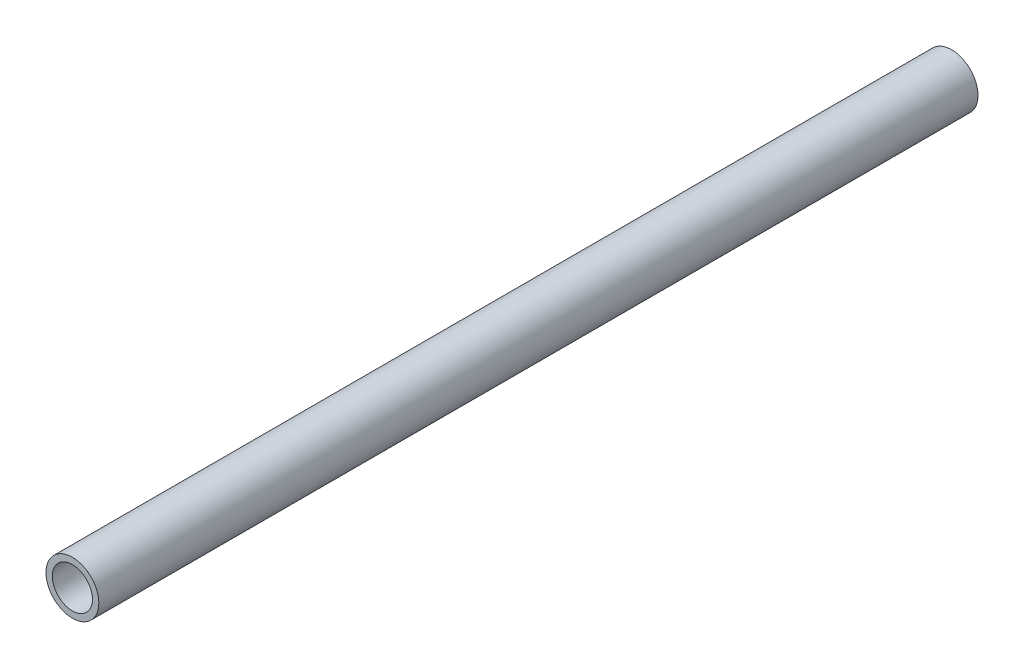
SolidWorks part; units mm, degrees
material "AISI 1020"
ref_plane "Plan de face" through (0, 0, 0) normal (0, 0, 1) x (1, 0, 0)
ref_plane "Plan de dessus" through (0, 0, 0) normal (0, 1, 0) x (1, 0, 0)
ref_plane "Plan de droite" through (0, 0, 0) normal (1, 0, 0) x (0, 0, -1)
sketch "Esquisse1" plane through (0, 0, 0) normal (0, 0, 1) x (1, 0, 0)
  circle A0 centre (0, 0) radius 4.57
  circle A1 centre (0, 0) radius 3.47
  dimension "D1" = 9.14
  dimension "D2" = 1.1
extrude "Boss.-Extru.1" add sketch "Esquisse1" along normal blind 152
sketch "Esquisse2" plane through (0, 0, 152) normal (0, 0, 1) x (1, 0, 0)
  circle A0 centre (0, 0) radius 4
  dimension "D1" = 8
extrude "Boss.-Extru.2" [suppressed] add sketch "Esquisse2" along normal blind 149.1
